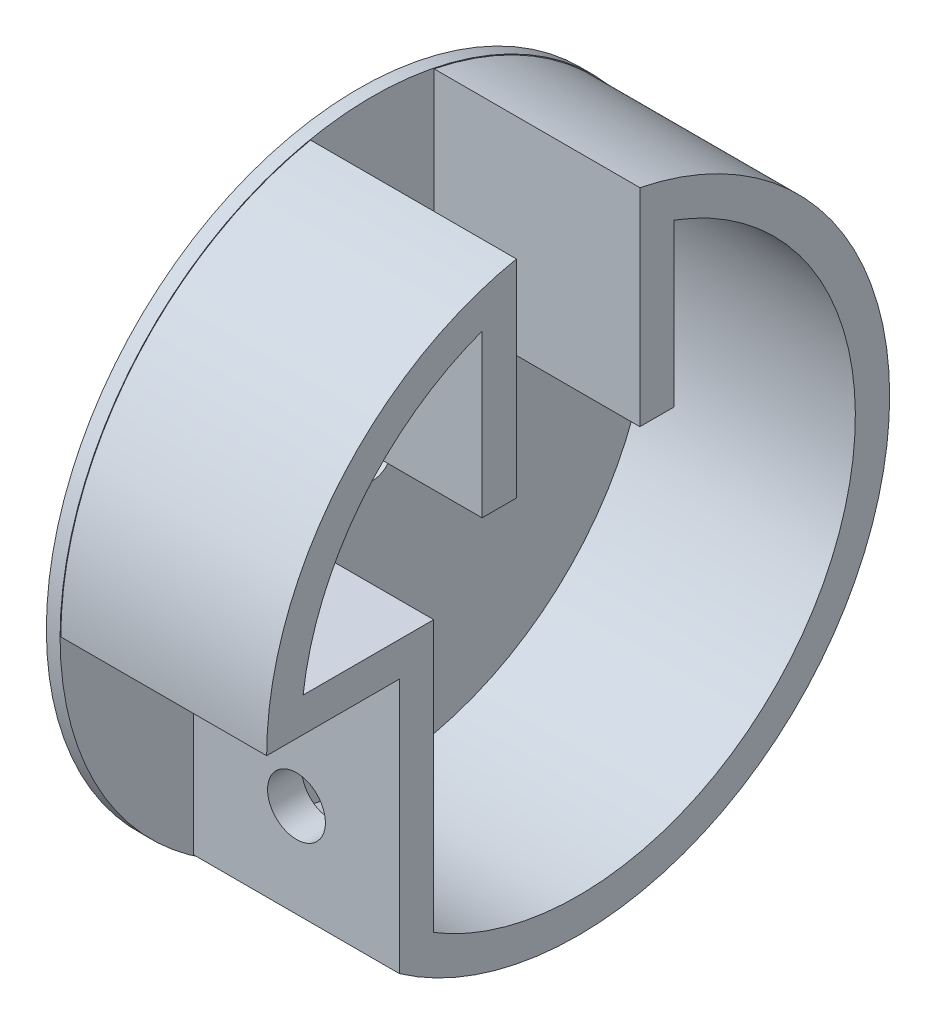
SolidWorks part; units mm, degrees
ref_plane "Piano frontale" through (0, 0, 0) normal (0, 0, 1) x (1, 0, 0)
ref_plane "Piano superiore" through (0, 0, 0) normal (0, 1, 0) x (1, 0, 0)
ref_plane "Piano destro" through (0, 0, 0) normal (1, 0, 0) x (0, 0, -1)
sketch "Schizzo1" plane through (0, 0, 0) normal (1, 0, 0) x (0, 0, -1)
  line L0 (-45.4016, 0) -> (-26.054, 0)
  line L1 (-26.054, 0) -> (-26.054, -37.1819)
  line L2 (-9, 44.5006) -> (-9, 14.3258)
  line L3 (-9, 14.3258) -> (9, 14.3258)
  line L4 (9, 44.5006) -> (9, 14.3258)
  line L5 (0, 45.4016) -> (0, -30) construction
  arc A1 (9, 44.5006) -> (-26.054, -37.1819) centre (0, 0) cw
  arc A2 (-26.054, -37.1819) -> (-9, -44.5006) centre (0, 0) ccw
  arc A3 (-45.4016, 0) -> (-9, 44.5006) centre (0, 0) cw
  point P6 (0, 14.3258)
  dimension "D1" = 18
extrude "Estrusione-Estrusione1" add sketch "Schizzo1" along normal blind 30 contours A1 L0 L1 region at (0, -1.693, -3.163)
shell "Svuota4" thickness 5 removed face at (30, 9.3432, 7.886) removed face at (0, 9.3432, 7.886) removed face at (15, 14.3258, 0)
sketch "Schizzo2" plane through (0, 0, 0) normal (-1, 0, 0) x (0, 0, 1)
  circle A0 centre (0, 0) radius 45.5106
  circle A1 centre (0, 0) radius 3
  dimension "D1" = 6
extrude "Estrusione-Estrusione2" add sketch "Schizzo2" along normal blind 2
sketch "Schizzo4" plane through (30, 0, 0) normal (1, 0, 0) x (0, 0, -1)
hole_wizard "Foro per Vite 5/16-1" positions "Schizzo3D1" profile "Schizzo5" hole size "5/16" standard "Ansi Inch" end condition up to next
sketch3d "Schizzo3D1"
  line L0 (0, 0, 26.054) -> (0, -37.1819, 26.054) construction
  point P0 (15, -23.5303, 26.054)
  dimension "D1" = 15
sketch "Schizzo5" plane through (15, -23.5303, 26.054) normal (1, 0, 0) x (0, -1, 0)
  line L0 (0, 0) -> (0, 5)
  line L1 (0, 5) -> (4.2164, 5)
  line L2 (4.2164, 5) -> (4.2164, 0)
  line L5 (4.2164, 0) -> (0, 0)
  line L11 (0, -6.35) -> (0, 107.95) construction
  dimension "Thru Hole Dia." = 8.4328
  dimension "Thru Hole Depth" = 5
